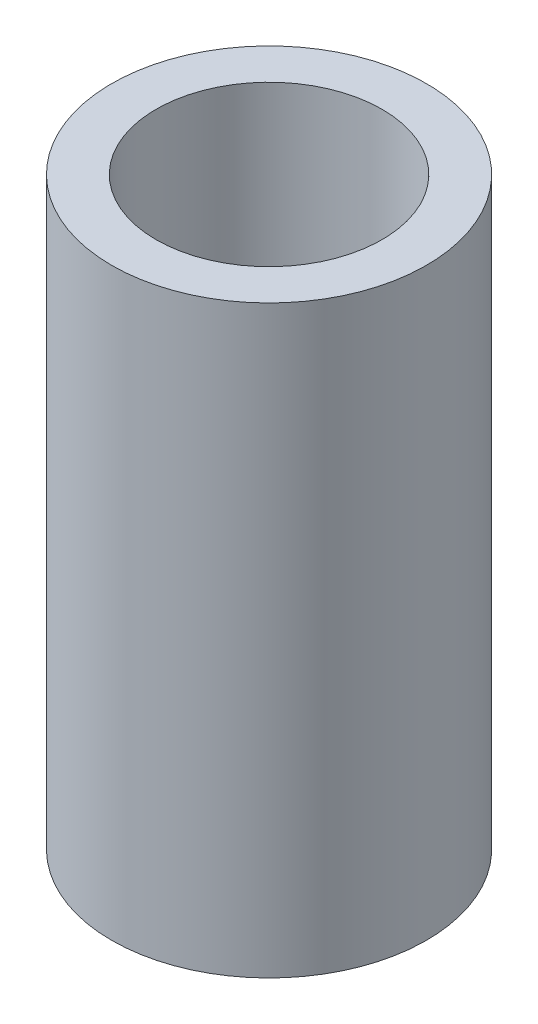
SolidWorks part; units mm, degrees
ref_plane "Front Plane" through (0, 0, 0) normal (0, 0, 1) x (1, 0, 0)
ref_plane "Top Plane" through (0, 0, 0) normal (0, 1, 0) x (1, 0, 0)
ref_plane "Right Plane" through (0, 0, 0) normal (1, 0, 0) x (0, 0, -1)
sketch "Sketch1" plane through (0, 0, 0) normal (0, 1, 0) x (1, 0, 0)
  circle A0 centre (0, 0) radius 25
  dimension "SLEEVE_OD" = 50
extrude "Boss-Extrude1" add sketch "Sketch1" along normal blind 92.8432
sketch "Sketch2" plane through (0, 0, 0) normal (0, 1, 0) x (1, 0, 0)
  circle A0 centre (0, 0) radius 17.9449
  dimension "BORE_D" = 35.8899
extrude "Cut-Extrude1" cut sketch "Sketch2" along normal through all
chamfer "Chamfer1" distance 3.2949 angle 60 rebuild error yes
